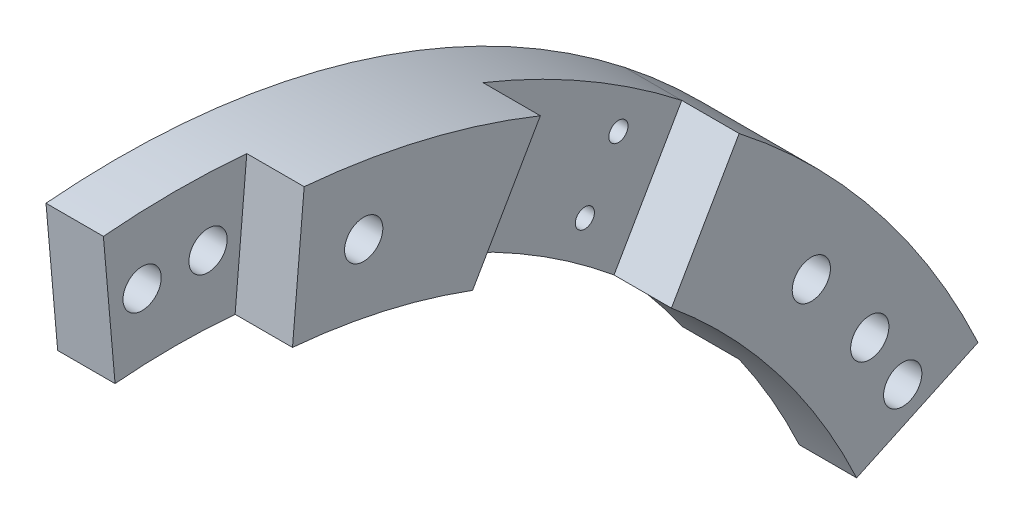
SolidWorks part; units mm, degrees
note: The reader was unsure of these and kept them because the rebuilt part matched: shared geometry of "Sketch1<8>", "Sketch1<10>".
ref_plane "Front Plane" through (0, 0, 0) normal (0, 0, 1) x (1, 0, 0)
ref_plane "Top Plane" through (0, 0, 0) normal (0, 1, 0) x (1, 0, 0)
ref_plane "Right Plane" through (0, 0, 0) normal (1, 0, 0) x (0, 0, -1)
sketch "Sketch1" plane through (0, 0, 0) normal (1, 0, 0) x (0, 0, -1)
  line L0 (0, 228.6) -> (0, 273.05)
  line L1 (197.9734, 114.3) -> (236.4682, 136.525)
  line L2 (197.9734, -114.3) -> (236.4682, -136.525)
  line L3 (0, -228.6) -> (0, -273.05)
  line L4 (-197.9734, -114.3) -> (-236.4682, -136.525)
  line L5 (-197.9734, 114.3) -> (-236.4682, 136.525)
  line L6 (0, 0) -> (43.5553, 247.0144)
  line L7 (0, 0) -> (0, 228.6)
  line L8 (0, 0) -> (43.5553, 247.0144) construction
  line L9 (0, 0) -> (125.4125, 217.2208) construction
  line L10 (0, 0) -> (10.9408, 250.5863)
  line L11 (0, 0) -> (10.9408, 250.5863) construction
  line L12 (0, 0) -> (222.4845, 115.8181) construction
  line L13 (0, 0) -> (23.7979, 272.011)
  line L14 (0, 0) -> (247.4673, 115.3959)
  line L15 (0, 0) -> (23.7979, 272.011) construction
  line L16 (0, 0) -> (247.4673, 115.3959) construction
  line L17 (-168.185, -215.1049) -> (102.1938, 253.2049)
  line L20 (-102.1938, -253.2049) -> (168.185, 215.1049)
  line L21 (-168.185, -215.1049) -> (168.185, 215.1049) construction
  line L22 (102.1938, 253.2049) -> (-102.1938, -253.2049) construction
  line L23 (0, 0) -> (236.4682, 136.525)
  line L24 (0, 0) -> (43.5553, 247.0144) construction
  line L25 (0, 0) -> (125.4125, 217.2208) construction
  line L26 (0, 0) -> (273.05, 0)
  line L27 (125.4125, 217.2208) -> (114.3, 197.9734)
  line L28 (125.4125, 217.2208) -> (136.525, 236.4682)
  line L29 (0, 0) -> (-23.7979, 272.011)
  line L30 (0, 0) -> (223.6695, 156.615)
  circle A0 centre (0, 0) radius 273.05
  circle A1 centre (0, 0) radius 228.6
  circle A2 centre (43.5553, 247.0144) radius 6.35
  arc A3 (0, 250.825) -> (217.2208, 125.4125) centre (0, 0) cw
  circle A5 centre (192.1431, 161.2272) radius 6.35
  circle A6 centre (235.6984, 85.7872) radius 6.35
  circle A7 centre (250.825, 0) radius 6.35
  circle A8 centre (235.6984, -85.7872) radius 6.35
  circle A9 centre (192.1431, -161.2272) radius 6.35
  circle A10 centre (125.4125, -217.2208) radius 6.35
  circle A11 centre (43.5553, -247.0144) radius 6.35
  circle A12 centre (-43.5553, -247.0144) radius 6.35
  circle A13 centre (-125.4125, -217.2208) radius 6.35
  circle A14 centre (-192.1431, -161.2272) radius 6.35
  circle A15 centre (-235.6984, -85.7872) radius 6.35
  circle A16 centre (-250.825, 0) radius 6.35
  circle A17 centre (-235.6984, 85.7872) radius 6.35
  circle A18 centre (-192.1431, 161.2272) radius 6.35
  circle A19 centre (-125.4125, 217.2208) radius 6.35
  circle A20 centre (-43.5553, 247.0144) radius 6.35
  circle A21 centre (10.9408, 250.5863) radius 6.35
  circle A22 centre (-10.9408, 250.5863) radius 6.35
  circle A23 centre (222.4845, 115.8181) radius 6.35
  circle A24 centre (211.5437, 134.7682) radius 6.35
  circle A25 centre (211.5437, -134.7682) radius 6.35
  circle A26 centre (222.4845, -115.8181) radius 6.35
  circle A27 centre (-10.9408, -250.5863) radius 6.35
  circle A28 centre (10.9408, -250.5863) radius 6.35
  circle A29 centre (-222.4845, -115.8181) radius 6.35
  circle A30 centre (-211.5437, -134.7682) radius 6.35
  circle A31 centre (-211.5437, 134.7682) radius 6.35
  circle A32 centre (-222.4845, 115.8181) radius 6.35
  circle A33 centre (125.4125, 217.2208) radius 6.35 [skipped]
  arc A34 (85.3371, 224.0082) -> (119.8563, 207.5971) centre (0, 0) cw
  circle A40 centre (102.9243, 216.4917) radius 3.175
  arc A43 (96.5803, 243.482) -> (130.9688, 226.8445) centre (0, 0) cw
  circle A44 centre (114.0782, 235.791) radius 3.175
  circle A45 centre (136.0252, 197.3809) radius 3.175
  circle A46 centre (147.1619, 216.6902) radius 3.175
  point P57 (0, 0)
  point P106 (130.9688, 226.8445)
  point P107 (119.8563, 207.5971)
  dimension "D1" = 546.1
  dimension "D2" = 457.2
  dimension "D5" = 18
  dimension "Bolt Size" = 12.7
  dimension "D8" = 12.7
  dimension "D18" = 6.35
  dimension "D19" = 5
  dimension "D4" = 10
  dimension "D6" = 20
  dimension "D7" = 2.5
  dimension "D10" = 60
  dimension "D11" = 250.825
  dimension "D12" = 5
  dimension "D14" = 273.05
  dimension "D15" = 60
  dimension "D16" = 76.2
  dimension "D17" = 20
  dimension "D3" = 6
  dimension "D9" = 6
  dimension "D13" = 2
extrude "Boss-Extrude9" add sketch "Sketch1" along normal blind 38.1 contours L13 A3 A2 L17 A0 | A3 A2 L6 A1 L17 | A3 L13 A1 L6 A2 | A3 A24 A5 L20 A1 L1 | A3 A24 L23 A0 L20 A5
extrude "Boss-Extrude10" add sketch "Sketch1<8>" along normal blind 19.05
sketch "Sketch1<8>" plane through (0, 0, 0) normal (1, 0, 0) x (0, 0, -1) same geometry as "Sketch1"
extrude "Boss-Extrude12" add sketch "Sketch1<10>" along normal blind 19.05 from offset 19.05 contours A3 A24 L23 A0 L30 | A3 A24 L30 A1 L1 | A1 L14 A0 L23 L1 A23
sketch "Sketch1<10>" plane through (0, 0, 0) normal (1, 0, 0) x (0, 0, -1) same geometry as "Sketch1"
